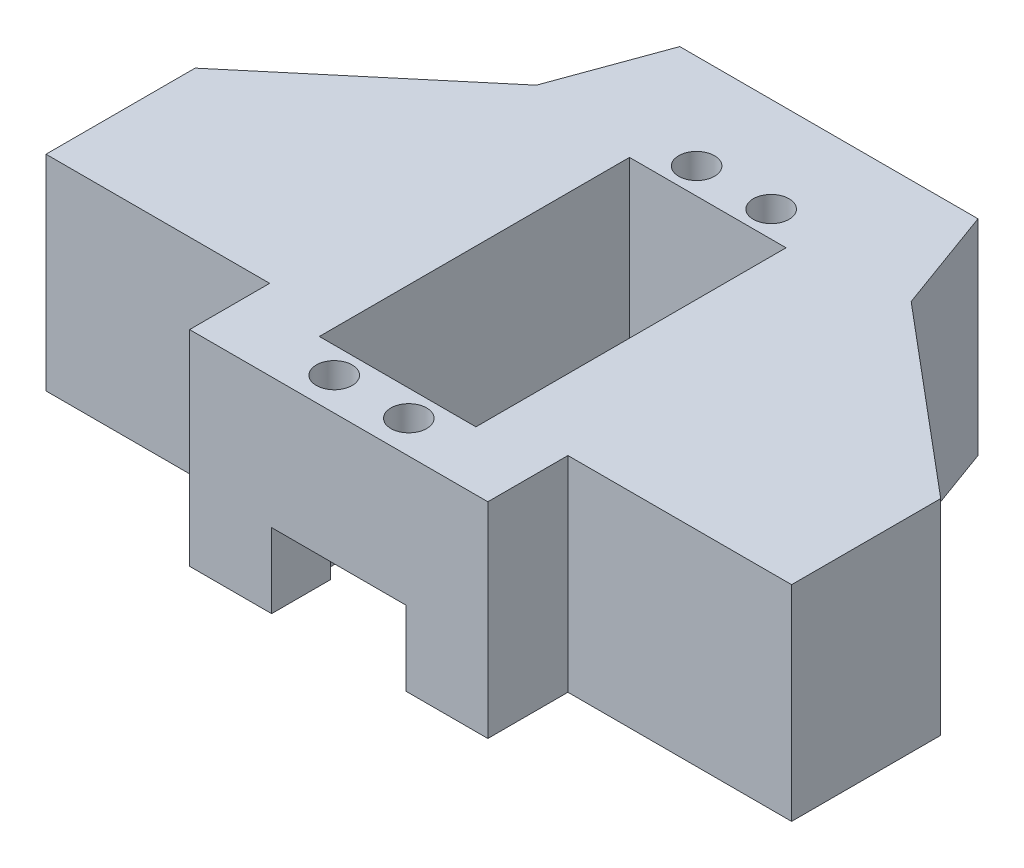
SolidWorks part; units mm, degrees
ref_plane "Front Plane" through (0, 0, 0) normal (0, 0, 1) x (1, 0, 0)
ref_plane "Top Plane" through (0, 0, 0) normal (0, 1, 0) x (1, 0, 0)
ref_plane "Right Plane" through (0, 0, 0) normal (1, 0, 0) x (0, 0, -1)
sketch "Sketch1" plane through (0, 0, 0) normal (0, 1, 0) x (1, 0, 0)
  line L0 (0, 0) -> (0, 55585.7092) construction
  line L1 (0, 0) -> (55585.7092, 0) construction
  line L2 (20, 55) -> (-20, 55)
  line L3 (-20, 55) -> (-25.1303, 40.9046)
  line L4 (-25.1303, 40.9046) -> (-50, 20)
  line L5 (-50, 20) -> (-50, 0)
  line L6 (-50, 0) -> (-20, 0)
  line L7 (-20, 0) -> (-20, -10.7407)
  line L8 (-20, -10.7407) -> (20, -10.7407)
  line L9 (20, 0) -> (20, -10.7407)
  line L10 (50, 0) -> (20, 0)
  line L11 (50, 20) -> (50, 0)
  line L12 (25.1303, 40.9046) -> (50, 20)
  line L13 (20, 55) -> (25.1303, 40.9046)
  point P14 (0, -10.7407)
  point P19 (0, 55)
  dimension "D1" = 40
  dimension "D2" = 40
  dimension "D3" = 20
  dimension "D4" = 100
  dimension "D5" = 110
  dimension "D6" = 55
  dimension "D7" = 10.7407
  dimension "D8" = 15
extrude "Boss-Extrude1" add sketch "Sketch1" along normal blind 27.5
sketch "Sketch2" plane through (0, 27.5, 0) normal (0, 1, 0) x (1, 0, 0)
  line L0 (0, -10.7407) -> (0, 49989.2593) construction
  line L1 (-20, -10.7407) -> (20, -10.7407) construction
  line L2 (0, -10.7407) -> (50000, -10.7407) construction
  line L3 (-6.4366, -8.7407) -> (49993.5634, -8.7407) construction
  line L4 (10.5, -2.8407) -> (-10.5, -2.8407)
  line L5 (-10.5, -2.8407) -> (-10.5, 38.7593)
  line L6 (-10.5, 38.7593) -> (10.5, 38.7593)
  line L7 (10.5, -2.8407) -> (10.5, 38.7593)
  circle A0 centre (-5, -6.3407) radius 2.4
  circle A1 centre (5, -6.3407) radius 2.4
  circle A2 centre (-5, 42.2593) radius 2.4
  circle A3 centre (5, 42.2593) radius 2.4
  point P4 (0, -10.7407)
  point P22 (0, -2.8407)
  point P23 (0, 38.7593)
  dimension "D1" = 4.8
  dimension "D4" = 4.8
  dimension "D2" = 2
  dimension "D3" = 10
  dimension "D5" = 48.6
  dimension "D6" = 10
  dimension "D7" = 21
  dimension "D8" = 3.5
  dimension "D9" = 3.5
extrude "Cut-Extrude1" cut sketch "Sketch2" against normal blind 30
sketch "Sketch3" plane through (0, 0, 10.7407) normal (0, 0, 1) x (1, 0, 0)
  line L0 (0, 0) -> (0, 50000) construction
  line L1 (0, 0) -> (50000, 0) construction
  line L3 (9, 10) -> (-9, 10)
  line L4 (-9, 10) -> (-9, 0)
  line L5 (-9, 0) -> (9, 0)
  line L6 (9, 10) -> (9, 0)
  point P10 (0, 0)
  point P11 (0, 10)
  dimension "D1" = 18
  dimension "D2" = 10
extrude "Cut-Extrude2" cut sketch "Sketch3" against normal up to surface (7.9 mm away) up to face at (0, 13.75, 2.8407)
